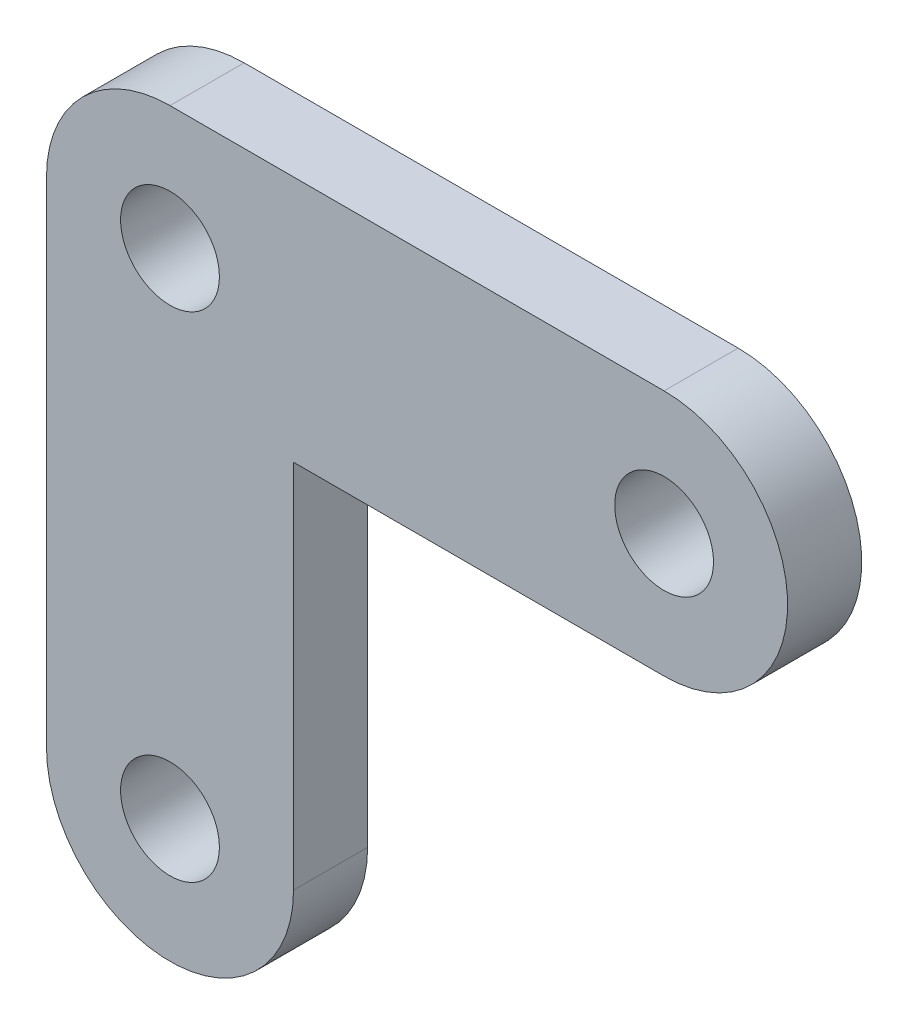
SolidWorks part; units mm, degrees
ref_plane "Front Plane" through (0, 0, 0) normal (0, 0, 1) x (1, 0, 0)
ref_plane "Top Plane" through (0, 0, 0) normal (0, 1, 0) x (1, 0, 0)
ref_plane "Right Plane" through (0, 0, 0) normal (1, 0, 0) x (0, 0, -1)
sketch "Sketch1" plane through (0, 0, 0) normal (0, 0, 1) x (1, 0, 0)
  line L2 (4.0012, 11.6661) -> (4.0012, 31.6661)
  line L3 (4.0012, 31.6661) -> (14.0012, 31.6661)
  line L4 (14.0012, 11.6661) -> (14.0012, 31.6661)
  line L5 (9.0012, 36.6661) -> (29.0012, 36.6661)
  line L6 (9.0012, 36.6661) -> (9.0012, 26.6661)
  line L7 (9.0012, 26.6661) -> (29.0012, 26.6661)
  arc A0 (4.0012, 11.6661) -> (14.0012, 11.6661) centre (9.0012, 11.6661) ccw
  circle A1 centre (9.0012, 11.6661) radius 2
  arc A2 (29.0012, 36.6661) -> (29.0012, 26.6661) centre (29.0012, 31.6661) cw
  circle A3 centre (29.0012, 31.6661) radius 2
  arc A4 (9.0012, 36.6661) -> (4.0012, 31.6661) centre (9.0012, 31.6661) ccw
  circle A5 centre (9.0012, 31.6661) radius 2
  point P4 (0, 0)
  point P5 (0, 0)
  point P6 (0, 0)
  point P20 (14.0012, 26.6661)
  point P27 (14.0012, 26.6661)
  dimension "D3" = 4
  dimension "D7" = 4
  dimension "D9" = 4
  dimension "D1" = 20
  dimension "D2" = 10
  dimension "D4" = 15
  dimension "D5" = 20
  dimension "D6" = 10
  dimension "D8" = 15
extrude "Boss-Extrude1" add sketch "Sketch1" along normal blind 3 contours A5 L3 L4 L7 A2 L5 L6 A3 | A5 L3 L2 A0 L4 L7 L6 A1 | A5 L6 L7 L4 L3 | A5 L6 A4 L3 region at (8.6998, 18.8125, 0) region at (6.6366, 34.0307, 0) region at (21.8548, 31.9675, 0) region at (11.7385, 28.9288, 0)
